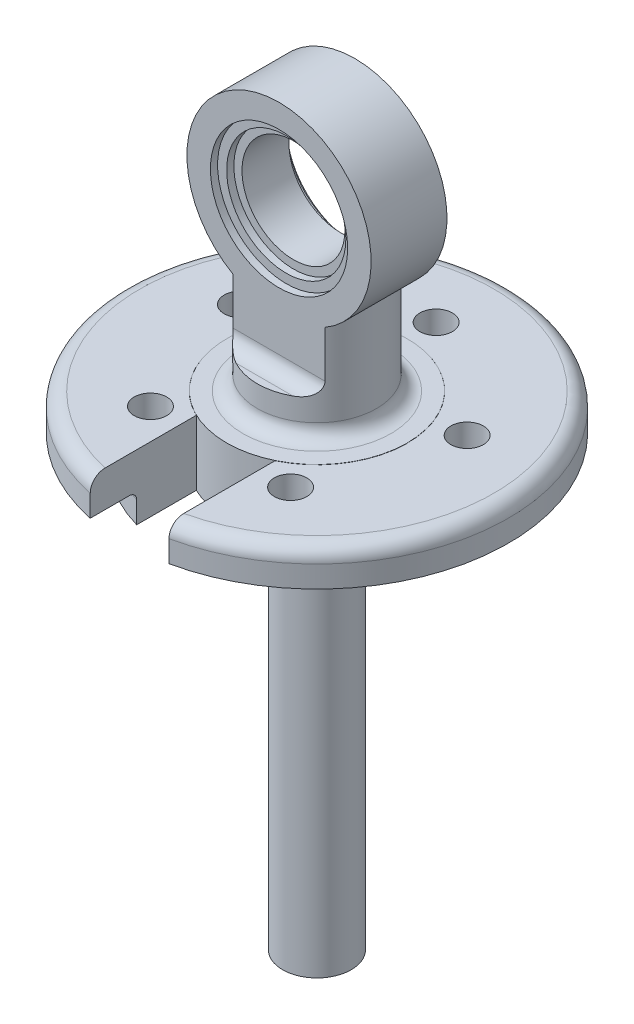
SolidWorks part; units mm, degrees
ref_plane "Front Plane" through (0, 0, 0) normal (0, 0, 1) x (1, 0, 0)
ref_plane "Top Plane" through (0, 0, 0) normal (0, 1, 0) x (1, 0, 0)
ref_plane "Right Plane" through (0, 0, 0) normal (1, 0, 0) x (0, 0, -1)
sketch "Sketch1" plane through (0, 0, 0) normal (0, 1, 0) x (1, 0, 0)
  circle A0 centre (0, 0) radius 4.75
  dimension "D1" = 9.5
extrude "Boss-Extrude1" add sketch "Sketch1" along normal blind 58
sketch "Sketch2" plane through (0, 58, 0) normal (0, 1, 0) x (1, 0, 0)
  circle A0 centre (0, 0) radius 9.45
  dimension "D1" = 18.9
extrude "Boss-Extrude2" add sketch "Sketch2" against normal blind 2.5
sketch "Sketch3" plane through (0, 58, 0) normal (0, 1, 0) x (1, 0, 0)
  circle A0 centre (0, 0) radius 20.25
  dimension "D1" = 40.5
extrude "Boss-Extrude3" add sketch "Sketch3" along normal blind 4 contours A0
sketch "Sketch4" plane through (0, 62, 0) normal (0, 1, 0) x (1, 0, 0)
  circle A0 centre (0, 0) radius 26.5
  dimension "D1" = 53
extrude "Boss-Extrude4" add sketch "Sketch4" along normal blind 5
fillet "Fillet2" radius 1 1 edges at (0, 62, 20.25)
fillet "Fillet3" radius 2 1 edges at (0, 67, 26.5)
sketch "Sketch6" plane through (0, 67, 0) normal (0, 1, 0) x (1, 0, 0)
  circle A0 centre (0, 0) radius 12.5
  dimension "D1" = 25
sketch "Sketch7" plane through (0, 67, 0) normal (0, 1, 0) x (1, 0, 0)
  circle A0 centre (0, 0) radius 8.25
extrude "Boss-Extrude5" add sketch "Sketch7" along normal blind 3.5
extrude "Boss-Extrude6" add sketch "Sketch6" along normal blind 0.03 contours A0
fillet "Fillet4" radius 2 1 edges at (0, 67.03, 8.25)
sketch "Sketch10" plane through (0, 67, 0) normal (0, 1, 0) x (1, 0, 0)
  circle A0 centre (0, 16.5) radius 2.25
  dimension "D1" = 4.5
extrude "Cut-Extrude2" cut sketch "Sketch10" against normal up to next contours A0
pattern_circular "CirPattern2" count 5 over 360 about axis through (0, 67, 0) along (0, 1, 0) of "Cut-Extrude2", "Boss-Extrude5"
sketch "Sketch11" plane through (0, 67, 0) normal (0, 1, 0) x (1, 0, 0)
  line L0 (-5.4485, -13.3488) -> (-5.4485, -11.2501)
  line L1 (5.4485, -13.3488) -> (5.4485, -26.5)
  line L2 (-5.4485, -13.3488) -> (-5.4485, -26.5)
  line L3 (-5.4485, -26.5) -> (5.4485, -26.5)
  line L5 (5.4485, -13.3488) -> (5.4485, -11.2501)
  circle A3 centre (0, 0) radius 12.5 construction
  arc A4 (-5.4485, -11.2501) -> (5.4485, -11.2501) centre (0, 0) ccw
extrude "Cut-Extrude3" cut sketch "Sketch11" against normal up to next
sketch "Sketch12" plane through (0, 70.5, 0) normal (0, 1, 0) x (1, 0, 0)
  circle A0 centre (0, 0) radius 8.25
extrude "Boss-Extrude7" add sketch "Sketch12" along normal blind 11.5
ref_plane "Plane2" through (0, 0, 5.25) normal (0, 0, 1) x (1, 0, 0)
ref_plane "Plane3" through (0, 0, -5.25) normal (0, 0, 1) x (1, 0, 0)
sketch "Sketch13" plane through (0, 0, 5.25) normal (0, 0, 1) x (1, 0, 0)
  line L2 (22.7729, 108.084) -> (-23.3682, 108.084)
  line L5 (-8.25, 72) -> (-23.3682, 72)
  line L6 (-23.3682, 72) -> (-23.3682, 108.084)
  line L7 (-23.3682, 108.084) -> (22.7729, 108.084)
  line L8 (22.7729, 108.084) -> (22.7729, 72)
  line L9 (22.7729, 72) -> (-8.25, 72)
  dimension "D1" = 10
ref_plane "Plane4" through (0, 0, 8.25) normal (0, 0, 1) x (1, 0, 0)
sketch "Sketch14" plane through (0, 0, 8.25) normal (0, 0, 1) x (1, 0, 0)
  line L0 (-23.3682, 108.084) -> (-23.3682, 72)
  line L1 (-23.3682, 72) -> (22.7729, 72)
  line L2 (22.7729, 72) -> (22.7729, 108.084)
  line L3 (22.7729, 108.084) -> (-23.3682, 108.084)
extrude "Cut-Extrude4" cut sketch "Sketch14" against normal blind 3
ref_plane "Plane5" through (0, 0, -8.25) normal (0, 0, 1) x (1, 0, 0)
sketch "Sketch15" plane through (0, 0, -8.25) normal (0, 0, 1) x (1, 0, 0)
  line L0 (22.7729, 72) -> (22.7729, 108.084)
  line L1 (22.7729, 108.084) -> (-23.3682, 108.084)
  line L2 (-23.3682, 108.084) -> (-23.3682, 72)
  line L3 (-23.3682, 72) -> (22.7729, 72)
extrude "Cut-Extrude6" cut sketch "Sketch15" along normal blind 3
fillet "Fillet5" radius 2 1 edges at (0, 72, -5.25)
fillet "Fillet6" radius 2 1 edges at (0, 72, 5.25)
sketch "Sketch16" plane through (0, 0, 5.25) normal (0, 0, 1) x (1, 0, 0)
  line L0 (0, 82) -> (0, 91.5)
  line L1 (-6.364, 82) -> (6.364, 82) construction
  circle A0 centre (0, 91.5) radius 12.75
  dimension "D2" = 25.5
  dimension "D1" = 9.5
extrude "Boss-Extrude8" add sketch "Sketch16" against normal blind 10.5 contours A0
sketch "Sketch17" plane through (0, 0, 5.25) normal (0, 0, 1) x (1, 0, 0)
  circle A1 centre (0, 91.5) radius 9.5
  dimension "D1" = 19
extrude "Cut-Extrude9" cut sketch "Sketch17" against normal blind 1 contours A1
sketch "Sketch18" plane through (0, 0, 4.25) normal (0, 0, 1) x (1, 0, 0)
  circle A0 centre (0, 91.5) radius 8.25
  dimension "D1" = 16.5
extrude "Cut-Extrude10" cut sketch "Sketch18" against normal blind 1
sketch "Sketch19" plane through (0, 0, 3.25) normal (0, 0, 1) x (1, 0, 0)
  circle A0 centre (0, 91.5) radius 7.125
  dimension "D1" = 14.25
extrude "Cut-Extrude11" cut sketch "Sketch19" against normal up to next
mirror "Mirror1" about plane through (0, 0, 0) normal (0, 0, 1) of "Cut-Extrude9"
mirror "Mirror2" about plane through (0, 0, 0) normal (0, 0, 1) of "Cut-Extrude10"
sketch "Sketch20" plane through (0, 0, 0) normal (0, 0, 1) x (1, 0, 0)
  circle A0 centre (0, 91.5) radius 7.25
  dimension "D1" = 14.5
ref_plane "Plane6" through (0, 91.5, 0) normal (0, 1, 0) x (1, 0, 0)
ref_axis "Axis1" through (0, 91.5, -29.1277) along (0, 0, 1)
sketch "Sketch21" plane through (0, 0, 3.25) normal (0, 0, 1) x (1, 0, 0)
  line L0 (3.8426, 85.5) -> (5.0426, 85.5)
  line L1 (3.8426, 97.5) -> (5.0426, 97.5)
  line L3 (3.8426, 97.5) -> (3.8426, 85.5)
  circle A0 centre (0, 91.5) radius 7.125 construction
  arc A1 (5.0426, 97.5) -> (5.0426, 85.5) centre (-0.1577, 91.5) cw
  dimension "D4" = 7.94
  dimension "D1" = 1.2
  dimension "D2" = 12
  dimension "D3" = 1.2
ref_axis "Axis2" through (29.15, 91.5, 0) along (-1, 0, 0)
ref_axis "Axis3" through (0, 109.4625, 0) along (0, -1, 0)
ref_point "Point1"
